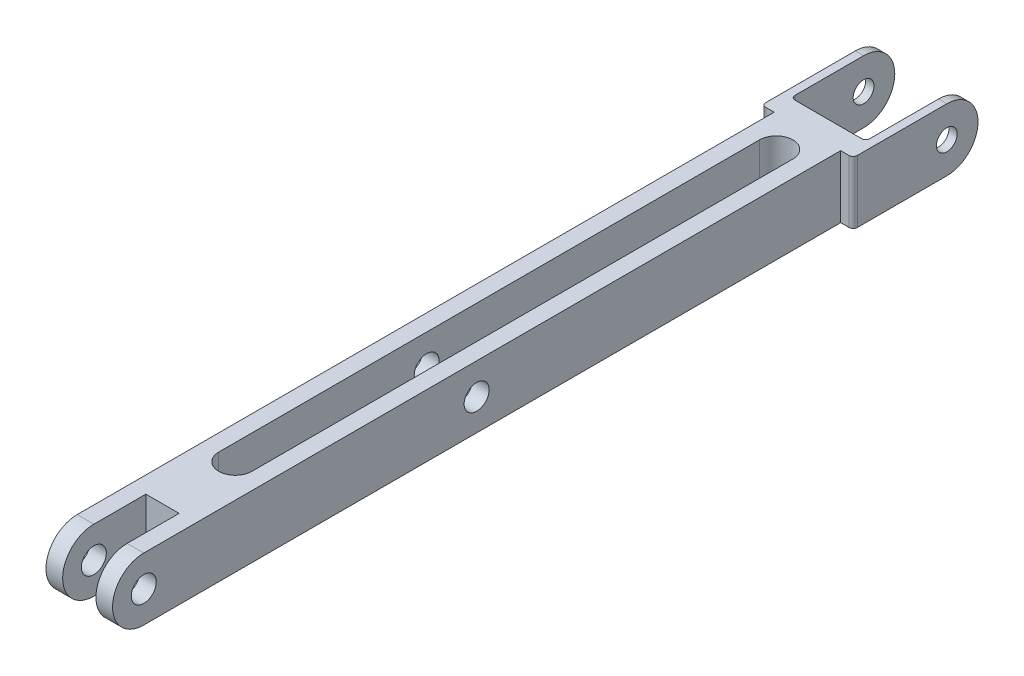
SolidWorks part; units mm, degrees
material "ABS"
ref_plane "前视基准面" through (0, 0, 0) normal (0, 0, 1) x (1, 0, 0)
ref_plane "上视基准面" through (0, 0, 0) normal (0, 1, 0) x (1, 0, 0)
ref_plane "右视基准面" through (0, 0, 0) normal (1, 0, 0) x (0, 0, -1)
sketch "草图2" plane through (0, 0, 0) normal (1, 0, 0) x (0, 0, -1)
  line L0 (-95, 7.5) -> (-95, -7.5) construction
  line L1 (-95, -7.5) -> (95, -7.5)
  line L3 (-95, 7.5) -> (95, 7.5)
  line L5 (-95, -7.5) -> (95, 7.5) construction
  line L6 (-95, 7.5) -> (95, -7.5) construction
  line L7 (95, 7.5) -> (95, -7.5) construction
  arc A0 (-95, 7.5) -> (-95, -7.5) centre (-95, 0) ccw
  arc A1 (95, 7.5) -> (95, -7.5) centre (95, 0) cw
  point P0 (0, 0)
  dimension "D1" = 15
  dimension "D2" = 190
extrude "凸台-拉伸1" add sketch "草图2" along normal blind 16
sketch "草图3" plane through (0, 7.5, 0) normal (0, 1, 0) x (1, 0, 0)
  line L1 (4, -102.5) -> (4, -82.5)
  line L2 (0, -102.5) -> (16, -102.5) construction
  line L3 (4, -82.5) -> (12, -82.5)
  line L4 (12, -82.5) -> (12, -102.5)
  line L5 (12, -102.5) -> (4, -102.5)
  line L6 (0, 95) -> (0, -95) construction
  line L7 (16, 95) -> (16, -95) construction
  line L10 (4, 102.5) -> (12, 102.5)
  line L14 (4, 102.5) -> (4, 77.5)
  line L15 (4, 77.5) -> (12, 77.5)
  line L16 (12, 77.5) -> (12, 102.5)
  line L17 (16, 95) -> (0, 95) construction
  dimension "D1" = 4
  dimension "D2" = 4
  dimension "D3" = 20
  dimension "D4" = 8
  dimension "D5" = 25
  dimension "D6" = 7.5
  dimension "D7" = 4
extrude "切除-拉伸1" cut sketch "草图3" against normal through all
sketch "草图4" plane through (16, 0, 0) normal (1, 0, 0) x (0, 0, -1)
  circle A0 centre (-95, 0) radius 3
  circle A1 centre (95, 0) radius 6
  dimension "D1" = 6
  dimension "D2" = 12
extrude "切除-拉伸2" cut sketch "草图4" against normal through all
sketch "草图5" plane through (0, -7.5, 0) normal (0, -1, 0) x (1, 0, 0)
  line L0 (8, 65) -> (8, -65) construction
  line L1 (12, 65) -> (12, -65)
  line L2 (4, 65) -> (4, -65)
  line L3 (0, 0) -> (8, 0) construction
  line L4 (0, 95) -> (0, -95) construction
  arc A0 (12, 65) -> (4, 65) centre (8, 65) ccw
  arc A1 (4, -65) -> (12, -65) centre (8, -65) ccw
  point P2 (8, 0)
  dimension "D1" = 8
  dimension "D2" = 8
  dimension "D3" = 130
extrude "切除-拉伸3" cut sketch "草图5" against normal through all
sketch "草图6" plane through (0, 0, 0) normal (-1, 0, 0) x (0, 0, 1)
  line L0 (15, 0) -> (0, 0) construction
  circle A1 centre (15, 0) radius 3
  circle A3 centre (95, 0) radius 3 construction
  dimension "D1" = 80
  dimension "D2" = 6
extrude "切除-拉伸4" cut sketch "草图6" against normal through all
sketch "草图7" plane through (0, -7.5, 0) normal (0, -1, 0) x (1, 0, 0)
  line L0 (8, 0) -> (8, -76.5378) construction
  line L1 (0, 95) -> (0, -95) construction
  line L2 (7.023, -77.5) -> (0, -77.5)
  line L3 (-1, -78.5) -> (-1, -102.5)
  line L4 (-1, -102.5) -> (-3, -102.5)
  line L5 (-3, -102.5) -> (-3, -73.5)
  line L6 (-2, -72.5) -> (0, -72.5)
  line L7 (7.023, -77.5) -> (8.977, -77.5)
  line L9 (19, -102.5) -> (19, -73.5)
  line L10 (17, -102.5) -> (19, -102.5)
  line L11 (17, -78.5) -> (17, -102.5)
  line L12 (8.977, -77.5) -> (16, -77.5)
  line L13 (16, -72.5) -> (16, -76.5378)
  line L14 (16, 95) -> (16, -95) construction
  line L15 (16, -76.5378) -> (0, -76.5378)
  line L16 (0, -76.5378) -> (0, -72.5)
  line L17 (16, -72.5) -> (18, -72.5)
  line L18 (8, -80.4495) -> (8, -147.5111) construction
  line L19 (4, -77.5) -> (12, -77.5) construction
  arc A0 (17, -78.5) -> (16, -77.5) centre (16, -78.5) ccw
  arc A1 (0, -77.5) -> (-1, -78.5) centre (0, -78.5) ccw
  arc A2 (-3, -73.5) -> (-2, -72.5) centre (-2, -73.5) cw
  arc A3 (19, -73.5) -> (18, -72.5) centre (18, -73.5) ccw
  point P15 (8, -77.5)
  point P16 (8, -80.4495)
  point P29 (17, -77.5)
  point P32 (-1, -77.5)
  point P35 (-3, -72.5)
  point P38 (19, -72.5)
  dimension "D5" = 1
  dimension "D1" = 8
  dimension "D2" = 18
  dimension "D3" = 2
  dimension "D4" = 5
  dimension "D6" = 25
extrude "凸台-拉伸2" add sketch "草图7" against normal up to surface (15 mm away) up to face at (8, 7.5, 0)
sketch "草图8" plane through (0, -7.5, 0) normal (0, -1, 0) x (-1, 0, 0)
  line L0 (-4, 77.5) -> (-12, 77.5) construction
  line L1 (-17, 102.5) -> (1, 102.5)
  line L2 (-17, 102.5) -> (-17, 78.5)
  line L3 (-16, 77.5) -> (0, 77.5)
  line L4 (1, 102.5) -> (1, 78.5)
  arc A0 (0, 77.5) -> (1, 78.5) centre (0, 78.5) ccw
  arc A1 (-17, 78.5) -> (-16, 77.5) centre (-16, 78.5) ccw
  dimension "D1" = 1
extrude "切除-拉伸5" cut sketch "草图8" against normal up to next
fillet "圆角1" radius 7.5 4 edges at (18, 7.5, -102.5) (18, -7.5, -102.5) (-2, 7.5, -102.5) (-2, -7.5, -102.5)
sketch "草图9" plane through (19, 0, 0) normal (1, 0, 0) x (0, 0, -1)
  circle A0 centre (95, 0) radius 2.5
  arc A1 (95, -7.5) -> (102.5, 0) centre (95, 0) ccw construction
  dimension "D1" = 5
extrude "切除-拉伸6" cut sketch "草图9" against normal through all
